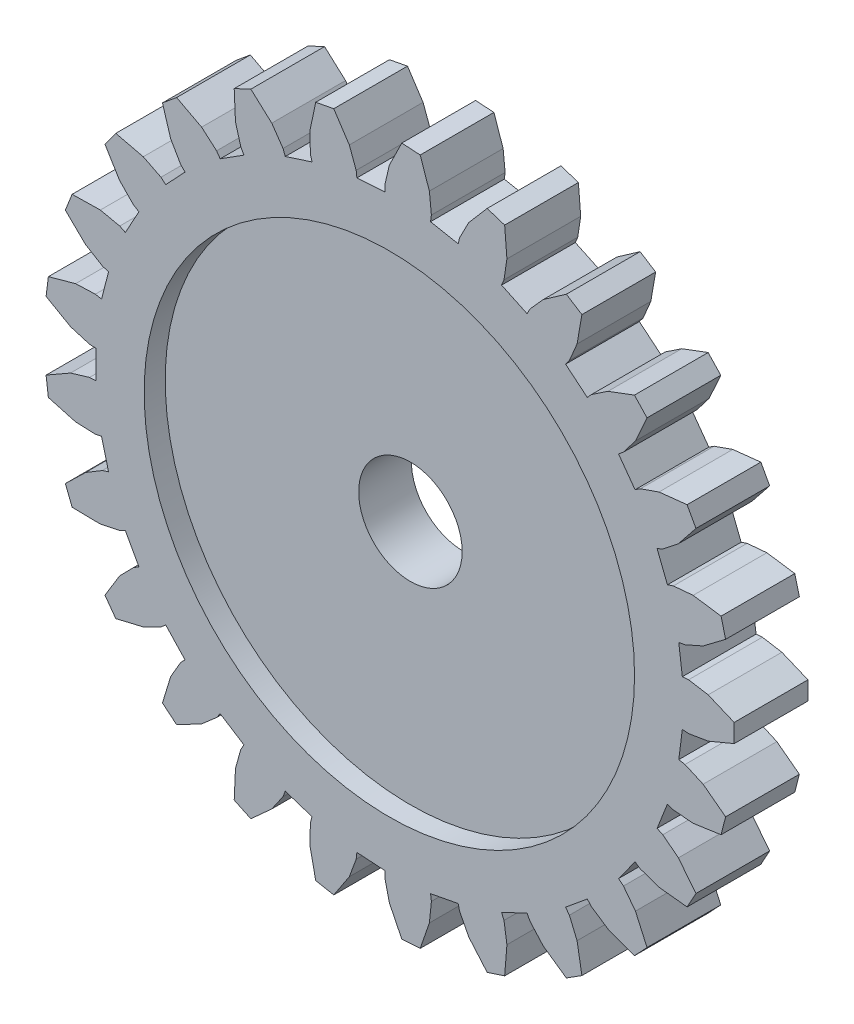
SolidWorks part; units mm, degrees
ref_plane "Front Plane" through (0, 0, 0) normal (0, 0, 1) x (1, 0, 0)
ref_plane "Top Plane" through (0, 0, 0) normal (0, 1, 0) x (1, 0, 0)
ref_plane "Right Plane" through (0, 0, 0) normal (1, 0, 0) x (0, 0, -1)
sketch "Model" plane through (0, 0, 0) normal (0, 0, 1) x (1, 0, 0)
  line L0 (122.7459, 141.0385) -> (123.3411, 141.0849)
  line L1 (123.3411, 141.0849) -> (125.1958, 140.7761)
  line L2 (125.1958, 140.7761) -> (127.6695, 139.7452)
  line L3 (127.6695, 139.7452) -> (127.6695, 137.9995)
  line L4 (127.6695, 137.9995) -> (125.1958, 136.9686)
  line L5 (125.1958, 136.9686) -> (123.3411, 136.6599)
  line L6 (123.3411, 136.6599) -> (122.7459, 136.7062)
  line L7 (122.7459, 136.7062) -> (122.4109, 134.0546)
  line L8 (122.4109, 134.0546) -> (122.999, 133.9515)
  line L9 (122.999, 133.9515) -> (124.7186, 133.1912)
  line L10 (124.7186, 133.1912) -> (126.8582, 131.5775)
  line L11 (126.8582, 131.5775) -> (126.4241, 129.8866)
  line L12 (126.4241, 129.8866) -> (123.7717, 129.5033)
  line L13 (123.7717, 129.5033) -> (121.8985, 129.6654)
  line L14 (121.8985, 129.6654) -> (121.3335, 129.8584)
  line L15 (121.3335, 129.8584) -> (120.3496, 127.3734)
  line L16 (120.3496, 127.3734) -> (120.8936, 127.1272)
  line L17 (120.8936, 127.1272) -> (122.3701, 125.9632)
  line L18 (122.3701, 125.9632) -> (124.0412, 123.8681)
  line L19 (124.0412, 123.8681) -> (123.2002, 122.3383)
  line L20 (123.2002, 122.3383) -> (120.5358, 122.6266)
  line L21 (120.5358, 122.6266) -> (118.7618, 123.2495)
  line L22 (118.7618, 123.2495) -> (118.2625, 123.5769)
  line L23 (118.2625, 123.5769) -> (116.6915, 121.4147)
  line L24 (116.6915, 121.4147) -> (117.1572, 121.041)
  line L25 (117.1572, 121.041) -> (118.2978, 119.5463)
  line L26 (118.2978, 119.5463) -> (119.3954, 117.1014)
  line L27 (119.3954, 117.1014) -> (118.2003, 115.8289)
  line L28 (118.2003, 115.8289) -> (115.6914, 116.7708)
  line L29 (115.6914, 116.7708) -> (114.128, 117.8153)
  line L30 (114.128, 117.8153) -> (113.7258, 118.2566)
  line L31 (113.7258, 118.2566) -> (111.6665, 116.5529)
  line L32 (111.6665, 116.5529) -> (112.0246, 116.0752)
  line L33 (112.0246, 116.0752) -> (112.7577, 114.3438)
  line L34 (112.7577, 114.3438) -> (113.2127, 111.7028)
  line L35 (113.2127, 111.7028) -> (111.7388, 110.7674)
  line L36 (111.7388, 110.7674) -> (109.5429, 112.3036)
  line L37 (109.5429, 112.3036) -> (108.2884, 113.7041)
  line L38 (108.2884, 113.7041) -> (108.0086, 114.2316)
  line L39 (108.0086, 114.2316) -> (105.5903, 113.0936)
  line L40 (105.5903, 113.0936) -> (105.8183, 112.5418)
  line L41 (105.8183, 112.5418) -> (106.0978, 110.6825)
  line L42 (106.0978, 110.6825) -> (105.8818, 108.0113)
  line L43 (105.8818, 108.0113) -> (104.2215, 107.4718)
  line L44 (104.2215, 107.4718) -> (102.4766, 109.5059)
  line L45 (102.4766, 109.5059) -> (101.6098, 111.1744)
  line L46 (101.6098, 111.1744) -> (101.47, 111.7548)
  line L47 (101.47, 111.7548) -> (98.8446, 111.254)
  line L48 (98.8446, 111.254) -> (98.9283, 110.6628)
  line L49 (98.9283, 110.6628) -> (98.7366, 108.7924)
  line L50 (98.7366, 108.7924) -> (97.8631, 106.2589)
  line L51 (97.8631, 106.2589) -> (96.1208, 106.1493)
  line L52 (96.1208, 106.1493) -> (94.9366, 108.5534)
  line L53 (94.9366, 108.5534) -> (94.512, 110.385)
  line L54 (94.512, 110.385) -> (94.5209, 110.982)
  line L55 (94.5209, 110.982) -> (91.8534, 111.1498)
  line L56 (91.8534, 111.1498) -> (91.7874, 110.5564)
  line L57 (91.7874, 110.5564) -> (91.1366, 108.7924)
  line L58 (91.1366, 108.7924) -> (89.6605, 106.5557)
  line L59 (89.6605, 106.5557) -> (87.9456, 106.8828)
  line L60 (87.9456, 106.8828) -> (87.3966, 109.5059)
  line L61 (87.3966, 109.5059) -> (87.4408, 111.3856)
  line L62 (87.4408, 111.3856) -> (87.5979, 111.9616)
  line L63 (87.5979, 111.9616) -> (85.056, 112.7875)
  line L64 (85.056, 112.7875) -> (84.8445, 112.2292)
  line L65 (84.8445, 112.2292) -> (83.7754, 110.6825)
  line L66 (83.7754, 110.6825) -> (81.7894, 108.8831)
  line L67 (81.7894, 108.8831) -> (80.2098, 109.6264)
  line L68 (80.2098, 109.6264) -> (80.3303, 112.3036)
  line L69 (80.3303, 112.3036) -> (80.8406, 114.1132)
  line L70 (80.8406, 114.1132) -> (81.136, 114.6321)
  line L71 (81.136, 114.6321) -> (78.8793, 116.0642)
  line L72 (78.8793, 116.0642) -> (78.5356, 115.576)
  line L73 (78.5356, 115.576) -> (77.1155, 114.3438)
  line L74 (77.1155, 114.3438) -> (74.7444, 113.0949)
  line L75 (74.7444, 113.0949) -> (73.3993, 114.2076)
  line L76 (73.3993, 114.2076) -> (74.1818, 116.7708)
  line L77 (74.1818, 116.7708) -> (75.1261, 118.3966)
  line L78 (75.1261, 118.3966) -> (75.5412, 118.8257)
  line L79 (75.5412, 118.8257) -> (73.7117, 120.774)
  line L80 (73.7117, 120.774) -> (73.2573, 120.3867)
  line L81 (73.2573, 120.3867) -> (71.5754, 119.5463)
  line L82 (71.5754, 119.5463) -> (68.9682, 118.9263)
  line L83 (68.9682, 118.9263) -> (67.9421, 120.3386)
  line L84 (67.9421, 120.3386) -> (69.3374, 122.6266)
  line L85 (69.3374, 122.6266) -> (70.6564, 123.9666)
  line L86 (70.6564, 123.9666) -> (71.1652, 124.279)
  line L87 (71.1652, 124.279) -> (69.8776, 126.6211)
  line L88 (69.8776, 126.6211) -> (69.3412, 126.3588)
  line L89 (69.3412, 126.3588) -> (67.5031, 125.9632)
  line L90 (67.5031, 125.9632) -> (64.8236, 126.011)
  line L91 (64.8236, 126.011) -> (64.181, 127.6342)
  line L92 (64.181, 127.6342) -> (66.1015, 129.5033)
  line L93 (66.1015, 129.5033) -> (67.7123, 130.4731)
  line L94 (67.7123, 130.4731) -> (68.2828, 130.6491)
  line L95 (68.2828, 130.6491) -> (67.6181, 133.2379)
  line L96 (67.6181, 133.2379) -> (67.0333, 133.1173)
  line L97 (67.0333, 133.1173) -> (65.1546, 133.1912)
  line L98 (65.1546, 133.1912) -> (62.5712, 133.9039)
  line L99 (62.5712, 133.9039) -> (62.3524, 135.6358)
  line L100 (62.3524, 135.6358) -> (64.6774, 136.9686)
  line L101 (64.6774, 136.9686) -> (66.4787, 137.5074)
  line L102 (66.4787, 137.5074) -> (67.0751, 137.536)
  line L103 (67.0751, 137.536) -> (67.0751, 140.2087)
  line L104 (67.0751, 140.2087) -> (66.4787, 140.2373)
  line L105 (66.4787, 140.2373) -> (64.6774, 140.7761)
  line L106 (64.6774, 140.7761) -> (62.3524, 142.1089)
  line L107 (62.3524, 142.1089) -> (62.5712, 143.8409)
  line L108 (62.5712, 143.8409) -> (65.1546, 144.5536)
  line L109 (65.1546, 144.5536) -> (67.0333, 144.6275)
  line L110 (67.0333, 144.6275) -> (67.6181, 144.5069)
  line L111 (67.6181, 144.5069) -> (68.2828, 147.0956)
  line L112 (68.2828, 147.0956) -> (67.7123, 147.2716)
  line L113 (67.7123, 147.2716) -> (66.1015, 148.2415)
  line L114 (66.1015, 148.2415) -> (64.181, 150.1106)
  line L115 (64.181, 150.1106) -> (64.8236, 151.7337)
  line L116 (64.8236, 151.7337) -> (67.5031, 151.7816)
  line L117 (67.5031, 151.7816) -> (69.3412, 151.3859)
  line L118 (69.3412, 151.3859) -> (69.8776, 151.1237)
  line L119 (69.8776, 151.1237) -> (71.1652, 153.4658)
  line L120 (71.1652, 153.4658) -> (70.6564, 153.7782)
  line L121 (70.6564, 153.7782) -> (69.3374, 155.1181)
  line L122 (69.3374, 155.1181) -> (67.9421, 157.4061)
  line L123 (67.9421, 157.4061) -> (68.9682, 158.8185)
  line L124 (68.9682, 158.8185) -> (71.5754, 158.1984)
  line L125 (71.5754, 158.1984) -> (73.2573, 157.3581)
  line L126 (73.2573, 157.3581) -> (73.7117, 156.9707)
  line L127 (73.7117, 156.9707) -> (75.5412, 158.919)
  line L128 (75.5412, 158.919) -> (75.1261, 159.3481)
  line L129 (75.1261, 159.3481) -> (74.1818, 160.974)
  line L130 (74.1818, 160.974) -> (73.3993, 163.5371)
  line L131 (73.3993, 163.5371) -> (74.7444, 164.6499)
  line L132 (74.7444, 164.6499) -> (77.1155, 163.401)
  line L133 (77.1155, 163.401) -> (78.5356, 162.1687)
  line L134 (78.5356, 162.1687) -> (78.8793, 161.6805)
  line L135 (78.8793, 161.6805) -> (81.136, 163.1126)
  line L136 (81.136, 163.1126) -> (80.8406, 163.6315)
  line L137 (80.8406, 163.6315) -> (80.3303, 165.4411)
  line L138 (80.3303, 165.4411) -> (80.2098, 168.1183)
  line L139 (80.2098, 168.1183) -> (81.7894, 168.8616)
  line L140 (81.7894, 168.8616) -> (83.7754, 167.0623)
  line L141 (83.7754, 167.0623) -> (84.8445, 165.5156)
  line L142 (84.8445, 165.5156) -> (85.056, 164.9572)
  line L143 (85.056, 164.9572) -> (87.5979, 165.7832)
  line L144 (87.5979, 165.7832) -> (87.4408, 166.3592)
  line L145 (87.4408, 166.3592) -> (87.3966, 168.2389)
  line L146 (87.3966, 168.2389) -> (87.9456, 170.8619)
  line L147 (87.9456, 170.8619) -> (89.6605, 171.189)
  line L148 (89.6605, 171.189) -> (91.1366, 168.9523)
  line L149 (91.1366, 168.9523) -> (91.7874, 167.1884)
  line L150 (91.7874, 167.1884) -> (91.8534, 166.595)
  line L151 (91.8534, 166.595) -> (94.5209, 166.7628)
  line L152 (94.5209, 166.7628) -> (94.512, 167.3598)
  line L153 (94.512, 167.3598) -> (94.9366, 169.1914)
  line L154 (94.9366, 169.1914) -> (96.1208, 171.5955)
  line L155 (96.1208, 171.5955) -> (97.8631, 171.4859)
  line L156 (97.8631, 171.4859) -> (98.7366, 168.9523)
  line L157 (98.7366, 168.9523) -> (98.9283, 167.0819)
  line L158 (98.9283, 167.0819) -> (98.8446, 166.4907)
  line L159 (98.8446, 166.4907) -> (101.47, 165.9899)
  line L160 (101.47, 165.9899) -> (101.6098, 166.5704)
  line L161 (101.6098, 166.5704) -> (102.4766, 168.2389)
  line L162 (102.4766, 168.2389) -> (104.2215, 170.2729)
  line L163 (104.2215, 170.2729) -> (105.8818, 169.7335)
  line L164 (105.8818, 169.7335) -> (106.0978, 167.0623)
  line L165 (106.0978, 167.0623) -> (105.8183, 165.203)
  line L166 (105.8183, 165.203) -> (105.5903, 164.6512)
  line L167 (105.5903, 164.6512) -> (108.0086, 163.5132)
  line L168 (108.0086, 163.5132) -> (108.2884, 164.0406)
  line L169 (108.2884, 164.0406) -> (109.5429, 165.4411)
  line L170 (109.5429, 165.4411) -> (111.7388, 166.9774)
  line L171 (111.7388, 166.9774) -> (113.2127, 166.042)
  line L172 (113.2127, 166.042) -> (112.7577, 163.401)
  line L173 (112.7577, 163.401) -> (112.0246, 161.6696)
  line L174 (112.0246, 161.6696) -> (111.6665, 161.1918)
  line L175 (111.6665, 161.1918) -> (113.7258, 159.4882)
  line L176 (113.7258, 159.4882) -> (114.128, 159.9295)
  line L177 (114.128, 159.9295) -> (115.6914, 160.974)
  line L178 (115.6914, 160.974) -> (118.2003, 161.9159)
  line L179 (118.2003, 161.9159) -> (119.3954, 160.6433)
  line L180 (119.3954, 160.6433) -> (118.2978, 158.1984)
  line L181 (118.2978, 158.1984) -> (117.1572, 156.7037)
  line L182 (117.1572, 156.7037) -> (116.6915, 156.3301)
  line L183 (116.6915, 156.3301) -> (118.2625, 154.1678)
  line L184 (118.2625, 154.1678) -> (118.7618, 154.4952)
  line L185 (118.7618, 154.4952) -> (120.5358, 155.1181)
  line L186 (120.5358, 155.1181) -> (123.2002, 155.4065)
  line L187 (123.2002, 155.4065) -> (124.0412, 153.8767)
  line L188 (124.0412, 153.8767) -> (122.3701, 151.7816)
  line L189 (122.3701, 151.7816) -> (120.8936, 150.6175)
  line L190 (120.8936, 150.6175) -> (120.3496, 150.3714)
  line L191 (120.3496, 150.3714) -> (121.3335, 147.8864)
  line L192 (121.3335, 147.8864) -> (121.8985, 148.0793)
  line L193 (121.8985, 148.0793) -> (123.7717, 148.2415)
  line L194 (123.7717, 148.2415) -> (126.4241, 147.8582)
  line L195 (126.4241, 147.8582) -> (126.8582, 146.1673)
  line L196 (126.8582, 146.1673) -> (124.7186, 144.5536)
  line L197 (124.7186, 144.5536) -> (122.999, 143.7933)
  line L198 (122.999, 143.7933) -> (122.4109, 143.6902)
  line L199 (122.4109, 143.6902) -> (122.7459, 141.0385)
  circle A0 centre (94.9366, 138.8724) radius 4.9116
  circle A1 centre (94.9366, 138.8724) radius 23.2767
extrude "Boss-Extrude2" add sketch "Model" along normal blind 7 contours L199 L198 L197 L196 L195 L194 L193 L192 L191 L190 L189 L188 L187 L186 L185 L184 L183 L182 L181 L180 L179 L178 L177 L176 L175 L174 L173 L172 L171 L170 L169 L168 L167 L166 L165 L164 L163 L162 L161 L160 L159 L158 L157 L156 L155 L154 L153 L152 L151 L150 L149 region at (123.1153, 140.1399, 0)
extrude "Boss-Extrude3" add sketch "Model<4>" along normal blind 5 contours A1 A0 region at (72.3182, 138.8724, 0)
sketch "Model<4>" plane through (0, 0, 0) normal (0, 0, 1) x (1, 0, 0) same geometry as "Model"
